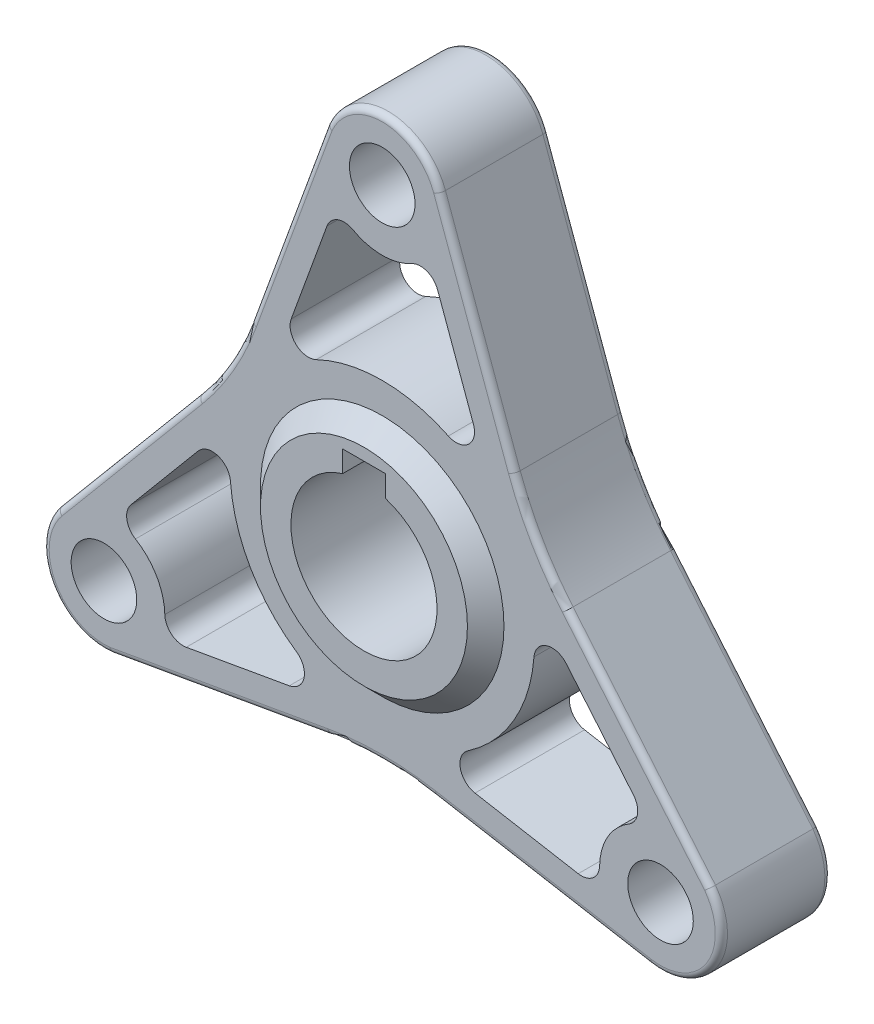
SolidWorks part; units mm, degrees
ref_plane "정면" through (0, 0, 0) normal (0, 0, 1) x (1, 0, 0)
ref_plane "윗면" through (0, 0, 0) normal (0, 1, 0) x (1, 0, 0)
ref_plane "우측면" through (0, 0, 0) normal (1, 0, 0) x (0, 0, -1)
sketch "스케치1" plane through (0, 0, 0) normal (0, 0, 1) x (1, 0, 0)
  line L0 (-9.076, 42.4163) -> (-14.957, 26.2584)
  line L1 (-9.1761, 56.7603) -> (-21.6211, 22.5678)
  line L2 (9.3969, 56.2056) -> (21.6724, 22.4789)
  line L3 (0, 0) -> (0, 52.7854) construction
  line L4 (9.0918, 42.425) -> (14.98, 26.2473)
  line L5 (4.6985, 54.4955) -> (20.592, 10.8284) construction
  line L6 (-4.4776, 55.0502) -> (-22.6781, 5.0448) construction
  line L7 (53.7439, -20.4335) -> (30.3549, 7.4405)
  line L8 (43.977, -36.2408) -> (8.6311, -30.0083)
  line L9 (32.1952, -29.0862) -> (15.2409, -26.0967)
  line L10 (41.2716, -13.3481) -> (30.2189, -0.1761)
  line L11 (-44.5678, -36.3269) -> (-8.7337, -30.0083)
  line L12 (-53.374, -19.9648) -> (-30.3035, 7.5294)
  line L13 (-41.287, -13.3388) -> (-30.2208, -0.1506)
  line L14 (-32.1956, -29.0682) -> (-15.262, -26.0823)
  line L15 (9.3969, 56.2056) -> (25.2905, 12.5385) construction
  line L16 (-9.1761, 56.7603) -> (-27.3765, 6.7549) construction
  circle A0 centre (0, 0) radius 52.7854 construction
  circle A1 centre (0, 52.7854) radius 5.3863
  arc A2 (-9.1761, 56.7603) -> (9.3969, 56.2056) centre (0, 52.7854) cw
  arc A3 (-4.813, 44.0199) -> (4.8252, 44.0266) centre (0, 52.7854) ccw
  circle A4 centre (0, 0) radius 20
  arc A5 (-10.8374, 22.5289) -> (10.8579, 22.519) centre (0, 0) cw
  arc A6 (10.8579, 22.519) -> (14.98, 26.2473) centre (12.1609, 25.2213) ccw
  arc A7 (-10.8374, 22.5289) -> (-14.957, 26.2584) centre (-12.1379, 25.2324) cw
  arc A8 (9.0918, 42.425) -> (4.8252, 44.0266) centre (6.2727, 41.3989) ccw
  arc A9 (-4.813, 44.0199) -> (-9.076, 42.4163) centre (-6.2569, 41.3902) ccw
  arc A10 (53.7439, -20.4335) -> (43.977, -36.2408) centre (45.7135, -26.3927) cw
  circle A11 centre (45.7135, -26.3927) radius 5.3863
  arc A12 (32.1952, -29.0862) -> (35.7155, -26.192) centre (32.7161, -26.1318) ccw
  arc A13 (40.5288, -17.8417) -> (35.7155, -26.192) centre (45.7135, -26.3927) ccw
  arc A14 (40.5288, -17.8417) -> (41.2716, -13.3481) centre (38.9734, -15.2765) ccw
  arc A15 (24.9293, -1.879) -> (30.2189, -0.1761) centre (27.9208, -2.1045) cw
  arc A16 (24.9293, -1.879) -> (14.0731, -20.6627) centre (0, 0) cw
  arc A17 (14.0731, -20.6627) -> (15.2409, -26.0967) centre (15.7618, -23.1423) ccw
  arc A18 (-44.5678, -36.3269) -> (-53.374, -19.9648) centre (-45.7135, -26.3927) cw
  circle A19 centre (-45.7135, -26.3927) radius 5.3863
  arc A20 (-41.287, -13.3388) -> (-40.5407, -17.8346) centre (-38.9888, -15.2671) ccw
  arc A21 (-35.7158, -26.1781) -> (-40.5407, -17.8346) centre (-45.7135, -26.3927) ccw
  arc A22 (-35.7158, -26.1781) -> (-32.1956, -29.0682) centre (-32.7165, -26.1137) ccw
  arc A23 (-14.0919, -20.6499) -> (-15.262, -26.0823) centre (-15.7829, -23.1279) cw
  arc A24 (-14.0919, -20.6499) -> (-24.931, -1.8563) centre (0, 0) cw
  arc A25 (-24.931, -1.8563) -> (-30.2208, -0.1506) centre (-27.9227, -2.079) ccw
  arc A26 (30.3549, 7.4405) -> (21.6724, 22.4789) centre (68.6571, 39.5799) cw
  arc A27 (8.6311, -30.0083) -> (-8.7337, -30.0083) centre (-0.0513, -79.2487) ccw
  arc A28 (-30.3035, 7.5294) -> (-21.6211, 22.5678) centre (-68.6058, 39.6688) ccw
  point P64 (0, 0)
  dimension "D1" = 10
  dimension "D6" = 5
  dimension "D7" = 3
  dimension "D9" = 50
  dimension "D2" = 20
  dimension "D3" = 20
  dimension "D4" = 5
  dimension "D5" = 5
  dimension "D8" = 3
extrude "보스-돌출1" add sketch "스케치1" along normal mid plane 18 contours A4 | A28 L12 A18 L11 A27 L8 A10 L7 A26 L2 A2 L1 A25 A24 A23 L14 A22 A21 A20 L13 A19 A17 A16 A15 L10 A14 A13 A12 L9 A11 A9 A3 A8 L4 A6 A5 A7 L0 A4 A1 region at (0.254, 61.2899, 0) region at (0, 0, 0)
extrude "보스-돌출2" add sketch "스케치1<3>" along normal mid plane 24 contours A4 region at (0, 0, 0)
sketch "스케치1<3>" plane through (0, 0, 0) normal (0, 0, 1) x (1, 0, 0) same geometry as "스케치1"
sketch "스케치2" plane through (0, 0, 0) normal (0, 0, 1) x (1, 0, 0)
  line L1 (-3.5, 15) -> (3.5, 15)
  line L2 (-3.5, 15) -> (-3.5, 11.4782)
  line L4 (3.5, 15) -> (3.5, 11.4782)
  arc A0 (-3.5, 11.4782) -> (3.5, 11.4782) centre (0, 0) ccw
  dimension "D1" = 7
  dimension "D3" = 27
  dimension "D2" = 3.5
extrude "컷-돌출1" cut sketch "스케치2" against normal through all both and the other way through all
chamfer "모따기1" distance 3 angle 45 2 edges at (20, 0, -12) (20, 0, 12)
fillet "필렛7" radius 1 12 edges at (25.3558, 14.5799, -9) (42.0494, -6.4965, -9) (54.2206, -31.649, -9) (26.3041, -33.1246, -9) (-0.0513, -29.2487, -9) (-26.6508, -33.1676, -9) (-54.5192, -31.132, -9) (-41.8387, -6.2177, -9) (15.5347, 39.3423, -9) (0.2985, 62.781, -9) (-15.3986, 39.6641, -9) (-25.3045, 14.6688, -9) tangent propagation no
fillet "필렛9" radius 1 12 edges at (0.2985, 62.781, 9) (42.0494, -6.4965, 9) (25.3558, 14.5799, 9) (54.2206, -31.649, 9) (26.3041, -33.1246, 9) (-0.0513, -29.2487, 9) (15.5347, 39.3423, 9) (-26.6508, -33.1676, 9) (-54.5192, -31.132, 9) (-41.8387, -6.2177, 9) (-25.3045, 14.6688, 9) (-15.3986, 39.6641, 9)
